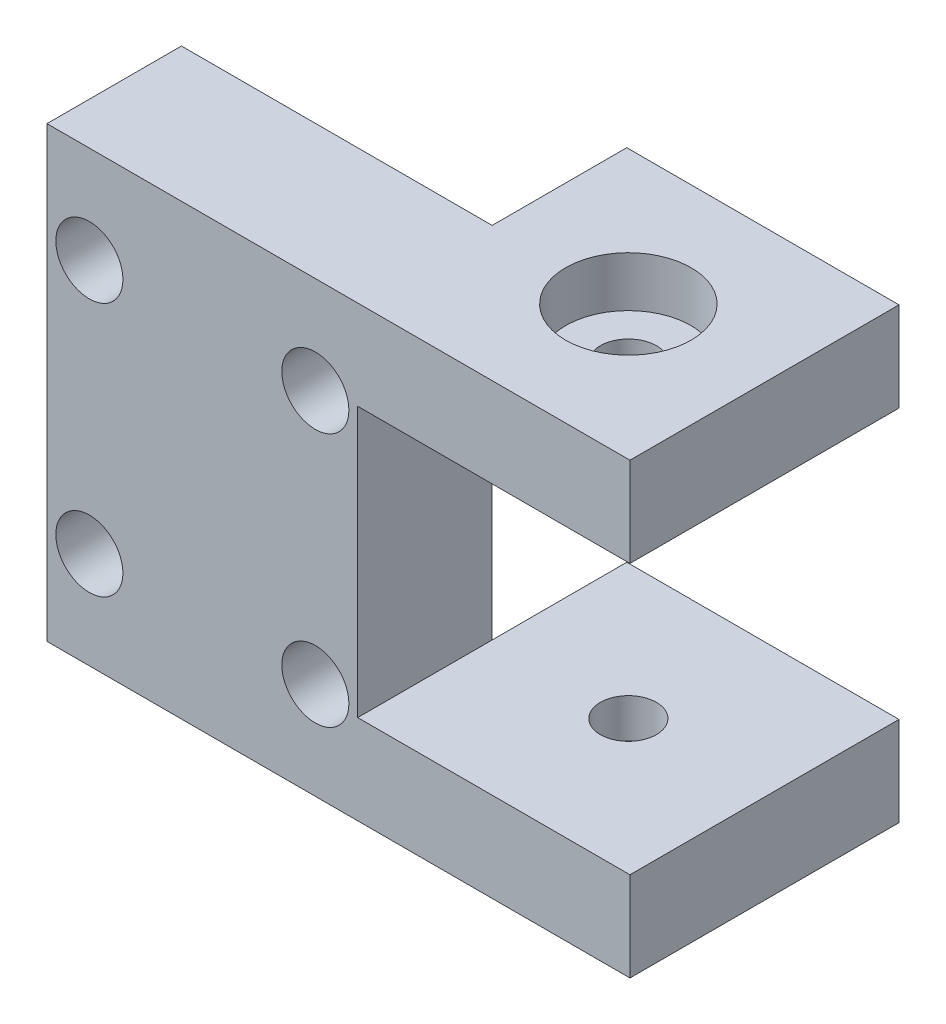
SolidWorks part; units mm, degrees
note: The reader was unsure of these and kept them because the rebuilt part matched: shared geometry of "Sketch1<3>", "Sketch2<3>", "Sketch2<4>", "Sketch3<3>".
ref_plane "Front Plane" through (0, 0, 0) normal (0, 0, 1) x (1, 0, 0)
ref_plane "Top Plane" through (0, 0, 0) normal (0, 1, 0) x (1, 0, 0)
ref_plane "Right Plane" through (0, 0, 0) normal (1, 0, 0) x (0, 0, -1)
sketch "Sketch1" plane through (0, 0, 0) normal (0, 0, 1) x (1, 0, 0)
  line L1 (-193.45, 31.75) -> (-149.45, 31.75)
  line L2 (-193.45, 31.75) -> (-193.45, -31.75)
  line L3 (-193.45, -31.75) -> (-149.45, -31.75)
  line L4 (-149.45, 31.75) -> (-149.45, -31.75)
  line L5 (-193.45, 31.75) -> (-149.45, -31.75) construction
  line L6 (-193.45, -31.75) -> (-149.45, 31.75) construction
  line L8 (-149.45, -31.75) -> (-110.9, -31.75)
  line L9 (-149.45, -31.75) -> (-149.45, -19.0888)
  line L10 (-192.45, -38.25) -> (-150.45, -38.25)
  line L11 (-150.45, -38.25) -> (-150.45, 38.25)
  line L12 (-150.45, 38.25) -> (-192.45, 38.25)
  line L13 (-192.45, 38.25) -> (-192.45, -38.25)
  line L14 (-192.45, -38.25) -> (-150.45, -38.25) construction
  line L15 (-150.45, -38.25) -> (-150.45, 38.25) construction
  line L16 (-150.45, 38.25) -> (-192.45, 38.25) construction
  line L17 (-192.45, 38.25) -> (-192.45, -38.25) construction
  line L18 (-149.45, -19.0888) -> (-110.9, -19.0888)
  line L19 (-110.9, -31.75) -> (-110.9, -19.0888)
  line L21 (-171.45, 0) -> (-160.4188, 0) construction
  line L22 (-149.45, 31.75) -> (-110.9, 31.75)
  line L23 (-149.45, 19.0888) -> (-110.9, 19.0888)
  line L24 (-110.9, 31.75) -> (-110.9, 19.0888)
  line L25 (-149.45, -19.038) -> (149.4496, -19.038) construction
  point P0 (-171.45, 0)
  point P8 (-171.45, -38.25)
  point P12 (-150.45, 0)
  dimension "D1" = 44
  dimension "D3" = 63.5
  dimension "D4" = 82.55
  dimension "D5" = 0.0508
  dimension "D2" = 0
extrude "Boss-Extrude1" add sketch "Sketch1" along normal up to vertex (19.038 mm away) contours L4 L1 L2 L3 | L8 L19 L18 L4 | L24 L22 L4 L23
extrude "Boss-Extrude2" add sketch "Sketch1<3>" against normal offset from surface (19.062 mm away) 38.1 contours L24 L22 L4 L23 | L8 L19 L18 L4 up to face at (-141.175, 0, 19.038)
sketch "Sketch1<3>" plane through (0, 0, 0) normal (0, 0, 1) x (1, 0, 0) same geometry as "Sketch1"
sketch "Sketch2" plane through (0, 0, 0) normal (0, 1, 0) x (1, 0, 0)
  line L0 (-149.45, 19.062) -> (-149.45, 0) construction
  line L1 (-149.45, -19.038) -> (-110.9, -19.038) construction
  line L2 (-149.45, -19.038) -> (-149.45, 19.062) construction
  line L3 (-149.45, 19.062) -> (-110.9, 19.062) construction
  line L4 (-110.9, -19.038) -> (-110.9, 19.062) construction
  line L5 (-149.45, -19.038) -> (-110.9, 19.062) construction
  line L6 (-149.45, 19.062) -> (-110.9, -19.038) construction
  circle A0 centre (-130.175, 0.012) radius 3.9687
  circle A1 centre (-130.175, 0.012) radius 8.89
  point P0 (-130.175, 0.012)
  dimension "D1" = 17.78
  dimension "D2" = 7.9375
extrude "Cut-Extrude1" cut sketch "Sketch2" against normal through all both and the other way through all contours A0
extrude "Cut-Extrude2" cut sketch "Sketch2<3>" along normal offset from surface 5.5575 and the other way through all from surface
sketch "Sketch2<3>" plane through (0, 0, 0) normal (0, 1, 0) x (1, 0, 0) same geometry as "Sketch2"
extrude "Cut-Extrude3" cut sketch "Sketch2<4>" against normal offset from surface (7.1037 mm away) 5.5575 from surface at 31.75 up to face at (-130.175, 19.0888, 3.9568) starting at face at (-130.175, 31.75, 3.9568)
sketch "Sketch2<4>" plane through (0, 0, 0) normal (0, 1, 0) x (1, 0, 0) same geometry as "Sketch2"
sketch "Sketch3" plane through (0, 0, 0) normal (0, 0, 1) x (1, 0, 0)
  circle A0 centre (-187.45, 18) radius 2.65
  circle A1 centre (-187.45, 18) radius 2.5
  circle A2 centre (-187.45, 18) radius 2.5 construction
  circle A3 centre (-187.45, -18) radius 2.5
  circle A4 centre (-187.45, -18) radius 2.5 construction
  circle A5 centre (-155.45, -18) radius 2.5
  circle A6 centre (-155.45, -18) radius 2.5 construction
  circle A7 centre (-155.45, 18) radius 2.5
  circle A8 centre (-155.45, 18) radius 2.5 construction
  circle A9 centre (-187.45, -18) radius 2.65
  circle A10 centre (-155.45, -18) radius 2.65
  circle A11 centre (-155.45, 18) radius 2.65
  circle A12 centre (-187.45, 18) radius 4.75
  circle A13 centre (-155.45, 18) radius 4.75
  circle A14 centre (-155.45, -18) radius 4.75
  circle A15 centre (-187.45, -18) radius 4.75
  dimension "D5" = 5.3
  dimension "D6" = 9.5
  dimension "D1" = 0
  dimension "D2" = 0
  dimension "D3" = 0
  dimension "D4" = 0
extrude "Cut-Extrude4" cut sketch "Sketch3" along normal through all contours A0 | A11 | A10 | A9
extrude "Cut-Extrude5" cut sketch "Sketch3<3>" against normal offset from surface (12.688 mm away) 6.35 from surface at 19.038 up to face at (-184.8, -18, 0) starting at face at (-184.8, -18, 19.038)
sketch "Sketch3<3>" plane through (0, 0, 0) normal (0, 0, 1) x (1, 0, 0) same geometry as "Sketch3"
